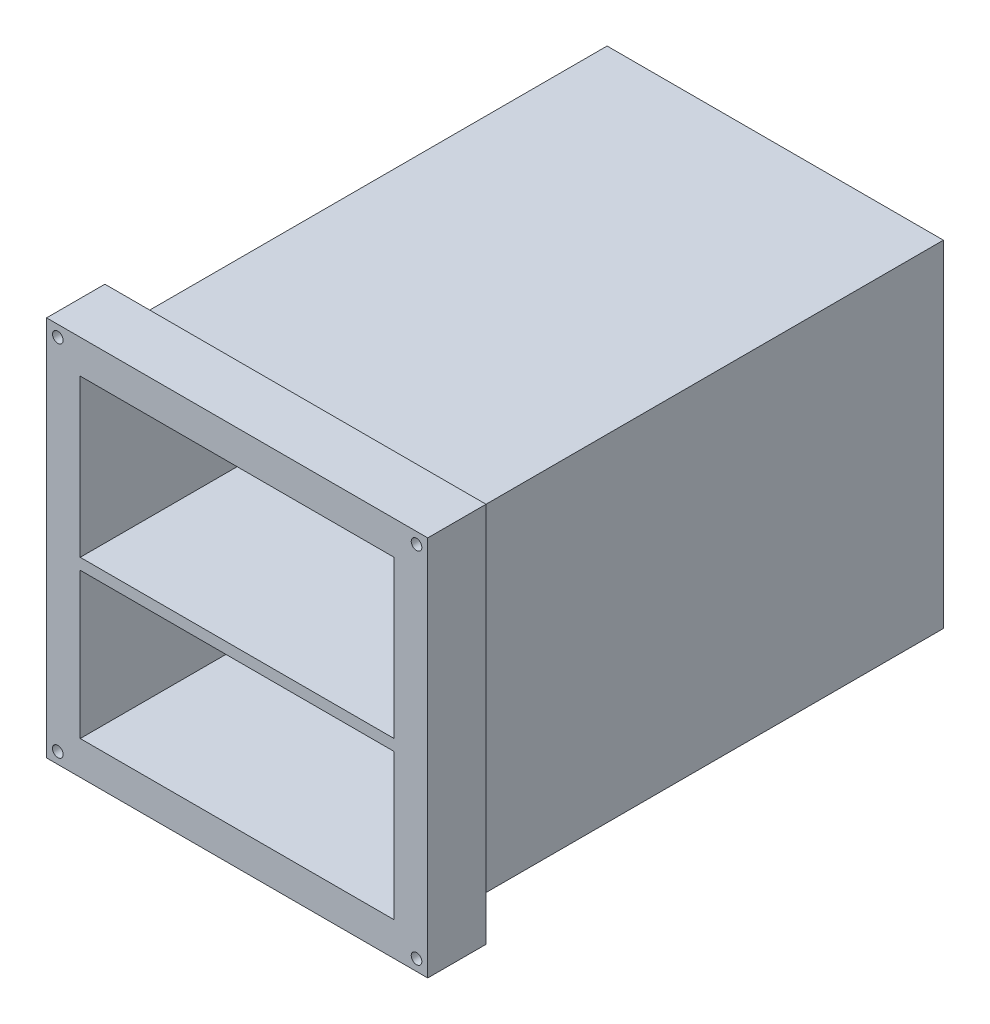
SolidWorks part; units mm, degrees
ref_plane "Front Plane" through (0, 0, 0) normal (0, 0, 1) x (1, 0, 0)
ref_plane "Top Plane" through (0, 0, 0) normal (0, 1, 0) x (1, 0, 0)
ref_plane "Right Plane" through (0, 0, 0) normal (1, 0, 0) x (0, 0, -1)
sketch "Sketch1" plane through (0, 0, 0) normal (0, 0, 1) x (1, 0, 0)
  line L1 (-47.625, 47.625) -> (47.625, 47.625)
  line L2 (-47.625, 47.625) -> (-47.625, -47.625)
  line L3 (-47.625, -47.625) -> (47.625, -47.625)
  line L4 (47.625, 47.625) -> (47.625, -47.625)
  line L5 (-47.625, 47.625) -> (47.625, -47.625) construction
  line L6 (-47.625, -47.625) -> (47.625, 47.625) construction
  point P0 (0, 0)
  dimension "D1" = 95.25
  dimension "D2" = 95.25
extrude "Boss-Extrude1" add sketch "Sketch1" along normal blind 152.4
sketch "Sketch2" plane through (0, 0, 152.4) normal (0, 0, 1) x (1, 0, 0)
  line L1 (-44.45, 44.45) -> (44.45, 44.45)
  line L2 (-44.45, 44.45) -> (-44.45, -44.45)
  line L3 (-44.45, -44.45) -> (44.45, -44.45)
  line L4 (44.45, 44.45) -> (44.45, -44.45)
  line L5 (-44.45, 44.45) -> (44.45, -44.45) construction
  line L6 (-44.45, -44.45) -> (44.45, 44.45) construction
  line L7 (-44.45, 44.45) -> (44.45, 44.45)
  line L8 (-44.45, 44.45) -> (-44.45, 0)
  line L9 (-44.45, 0) -> (44.45, 0)
  line L10 (44.45, 44.45) -> (44.45, 0)
  line L11 (-44.45, -44.45) -> (44.45, -44.45)
  line L12 (-44.45, -44.45) -> (-44.45, -3.175)
  line L13 (-44.45, -3.175) -> (44.45, -3.175)
  line L14 (44.45, -44.45) -> (44.45, -3.175)
  point P0 (0, 0)
  dimension "D1" = 88.9
  dimension "D2" = 88.9
  dimension "D3" = 3.175
  dimension "D4" = 44.45
extrude "Cut-Extrude1" cut sketch "Sketch2" against normal blind 139.7 contours L2 L9 L4 L1 region at (0, 22.225, 152.4)
extrude "Cut-Extrude2" cut sketch "Sketch2<3>" against normal blind 111.76 contours L13 L2 L3 L4 region at (0, -23.8125, 152.4)
sketch "Sketch2<3>" plane through (0, 0, 152.4) normal (0, 0, 1) x (1, 0, 0) same geometry as "Sketch2"
sketch "Sketch3" plane through (0, 0, 0) normal (0, 0, -1) x (-1, 0, 0)
  line L1 (-44.45, -3.175) -> (44.45, -3.175)
  line L2 (-44.45, -3.175) -> (-44.45, -44.45)
  line L3 (-44.45, -44.45) -> (44.45, -44.45)
  line L4 (44.45, -3.175) -> (44.45, -44.45)
  line L5 (-42.0326, -3.2045) -> (41.7874, -3.2045)
  line L6 (-42.0326, -3.2045) -> (-42.0326, -31.1445)
  line L7 (-42.0326, -31.1445) -> (41.7874, -31.1445)
  line L8 (41.7874, -3.2045) -> (41.7874, -31.1445)
  line L9 (-42.0326, -3.2045) -> (41.7874, -31.1445) construction
  line L10 (-42.0326, -31.1445) -> (41.7874, -3.2045) construction
  line L11 (-32.4154, -9.1288) -> (32.4154, -9.1288)
  line L12 (-32.4154, -9.1288) -> (-32.4154, -43.8445)
  line L13 (-32.4154, -43.8445) -> (32.4154, -43.8445)
  line L14 (32.4154, -9.1288) -> (32.4154, -43.8445)
  line L15 (-32.4154, -9.1288) -> (32.4154, -43.8445) construction
  line L16 (-32.4154, -43.8445) -> (32.4154, -9.1288) construction
  point P6 (-0.1226, -17.1745)
  point P11 (0, -7.5359)
  point P12 (0, -26.4867)
  point P17 (0, -4.5515)
  dimension "D1" = 83.82
  dimension "D2" = 27.94
  dimension "D3" = 12.7
sketch "Sketch5" plane through (0, 0, 152.4) normal (0, 0, 1) x (1, 0, 0)
  line L1 (-44.45, 44.45) -> (44.45, 44.45)
  line L2 (-44.45, 44.45) -> (-44.45, -44.45)
  line L3 (-44.45, -44.45) -> (44.45, -44.45)
  line L4 (44.45, 44.45) -> (44.45, -44.45)
  line L5 (-44.45, 44.45) -> (44.45, -44.45) construction
  line L6 (-44.45, -44.45) -> (44.45, 44.45) construction
  line L7 (-53.975, 53.975) -> (53.975, 53.975)
  line L8 (-53.975, 53.975) -> (-53.975, -53.975)
  line L9 (-53.975, -53.975) -> (53.975, -53.975)
  line L10 (53.975, 53.975) -> (53.975, -53.975)
  line L11 (-53.975, 53.975) -> (53.975, -53.975) construction
  line L12 (-53.975, -53.975) -> (53.975, 53.975) construction
  point P0 (0, 0)
  point P7 (0, 0)
  dimension "D1" = 107.95
extrude "Boss-Extrude2" add sketch "Sketch5" against normal blind 16.51
sketch "Sketch6" plane through (0, 0, 152.4) normal (0, 0, 1) x (1, 0, 0)
  line L1 (-50.8, 50.8) -> (50.8, 50.8)
  line L2 (-50.8, 50.8) -> (-50.8, -50.8)
  line L3 (-50.8, -50.8) -> (50.8, -50.8)
  line L4 (50.8, 50.8) -> (50.8, -50.8)
  line L5 (-50.8, 50.8) -> (50.8, -50.8) construction
  line L6 (-50.8, -50.8) -> (50.8, 50.8) construction
  circle A0 centre (-50.8, 50.8) radius 1.5
  circle A1 centre (50.8, 50.8) radius 1.5
  circle A2 centre (50.8, -50.8) radius 1.5
  circle A3 centre (-50.8, -50.8) radius 1.5
  point P0 (0, 0)
  dimension "D1" = 3
  dimension "D2" = 3
  dimension "D3" = 3
  dimension "D4" = 3
  dimension "D5" = 101.6
extrude "Cut-Extrude5" cut sketch "Sketch6" against normal blind 16.51 contours L1 A0 L2 | L4 A1 L1 | L2 A3 L3 | L3 A2 L4 | L4 A2 L3 | L3 A3 L2 | L2 A0 L1 | L1 A1 L4 region at (-51.0122, 51.0122, 152.4) region at (-50.1634, 50.1634, 152.4) region at (51.0122, 51.0122, 152.4) region at (50.1634, 50.1634, 152.4) region at (-50.1634, -50.1634, 152.4) region at (-51.0122, -51.0122, 152.4) region at (51.0122, -51.0122, 152.4) region at (50.1634, -50.1634, 152.4)
sketch "Sketch7" plane through (0, 0, 0) normal (0, 0, -1) x (-1, 0, 0)
  line L0 (44.45, 44.45) -> (44.45, -44.45) construction
  line L5 (-44.45, 0.9875) -> (44.45, -42.9924) construction
  line L6 (-44.45, -42.9924) -> (44.45, 0.9875) construction
  line L7 (-44.45, 44.45) -> (-44.45, -44.45) construction
  circle A0 centre (-44.45, 0.9875) radius 1.5
  circle A1 centre (44.45, 0.9875) radius 1.5
  circle A2 centre (44.45, -42.9924) radius 1.5
  circle A3 centre (-44.45, -42.9924) radius 1.5
  point P0 (0, -21.0025)
  point P11 (-44.45, 0.9875)
  point P14 (44.45, 0.9875)
  point P15 (44.45, -42.9924)
  dimension "D2" = 3
  dimension "D3" = 3
  dimension "D4" = 3
  dimension "D5" = 3
  dimension "D1" = 88.9
extrude "Cut-Extrude6" cut sketch "Sketch7" against normal blind 7.874
extrude "Cut-Extrude7" cut sketch "Sketch3" against normal blind 30.48 contours L11 L14 L7 L8 L5 L6 L12 | L14 L11 L12 L7 | L14 L7 L12 L13 region at (0.1226, -4.0881, 0) region at (0, -20.1367, 0) region at (0, -37.4945, 0)
sketch "Sketch8" plane through (0, 0, 30.48) normal (0, 0, -1) x (-1, 0, 0)
  line L0 (-32.4154, -43.8445) -> (32.4154, -43.8445) construction
  line L1 (-16.0476, -39.3694) -> (16.0476, -39.3694)
  line L2 (-16.0476, -39.3694) -> (-16.0476, -43.8445)
  line L3 (-16.0476, -43.8445) -> (16.0476, -43.8445)
  line L4 (16.0476, -39.3694) -> (16.0476, -43.8445)
  line L5 (-16.0476, -39.3694) -> (16.0476, -43.8445) construction
  line L6 (-16.0476, -43.8445) -> (16.0476, -39.3694) construction
  point P0 (0, -41.6069)
extrude "Cut-Extrude8" cut sketch "Sketch8" against normal blind 30.48
